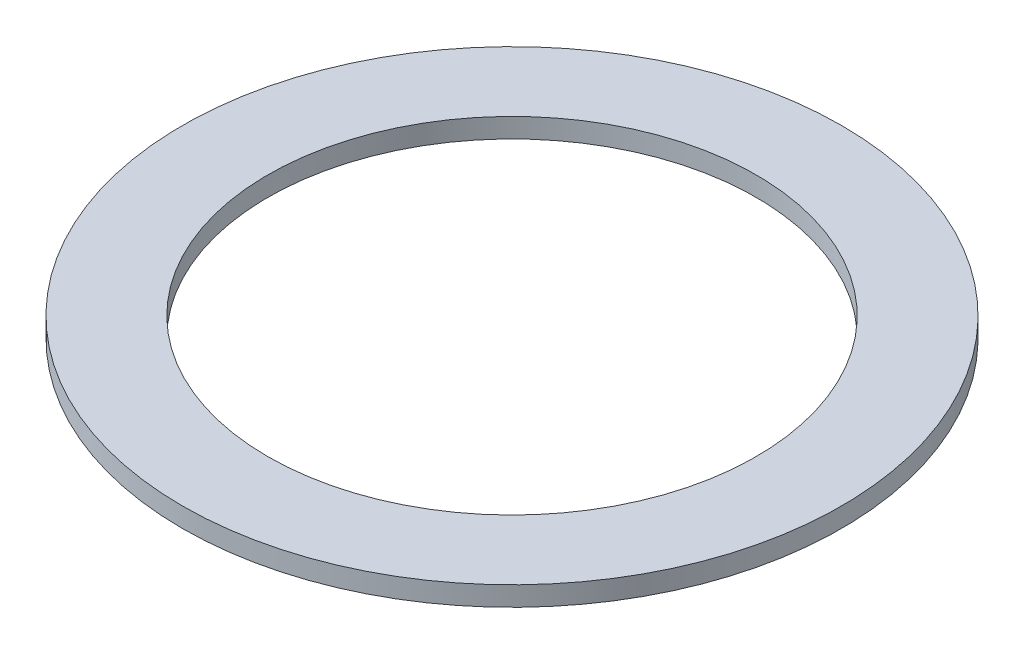
SolidWorks part; units mm, degrees
ref_plane "Front Plane" through (0, 0, 0) normal (0, 0, 1) x (1, 0, 0)
ref_plane "Top Plane" through (0, 0, 0) normal (0, 1, 0) x (1, 0, 0)
ref_plane "Right Plane" through (0, 0, 0) normal (1, 0, 0) x (0, 0, -1)
sketch "Sketch1" plane through (0, 0, 0) normal (0, 1, 0) x (1, 0, 0)
  circle A0 centre (0, 0) radius 67.5
  dimension "FLANGE_OD" = 135
extrude "Boss-Extrude1" add sketch "Sketch1" along normal blind 4
sketch "Sketch2" plane through (0, 0, 0) normal (0, 1, 0) x (1, 0, 0)
  circle A0 centre (0, 0) radius 50
  dimension "BORE_D" = 100
extrude "Cut-Extrude1" cut sketch "Sketch2" along normal through all
sketch "Sketch3" plane through (0, 4, 0) normal (0, 1, 0) x (1, 0, 0)
  circle A0 centre (0, 0) radius 28.8201 construction
  circle A1 centre (-28.8201, 0) radius 3.1221
  dimension "BOLT_D" = 6.2442
  dimension "BOLT_PCD" = 57.6401
extrude "Cut-Extrude2" cut sketch "Sketch3" against normal blind 3.8285 rebuild error yes
pattern_circular "CirPattern1" count 3 over 360 rebuild error yes
